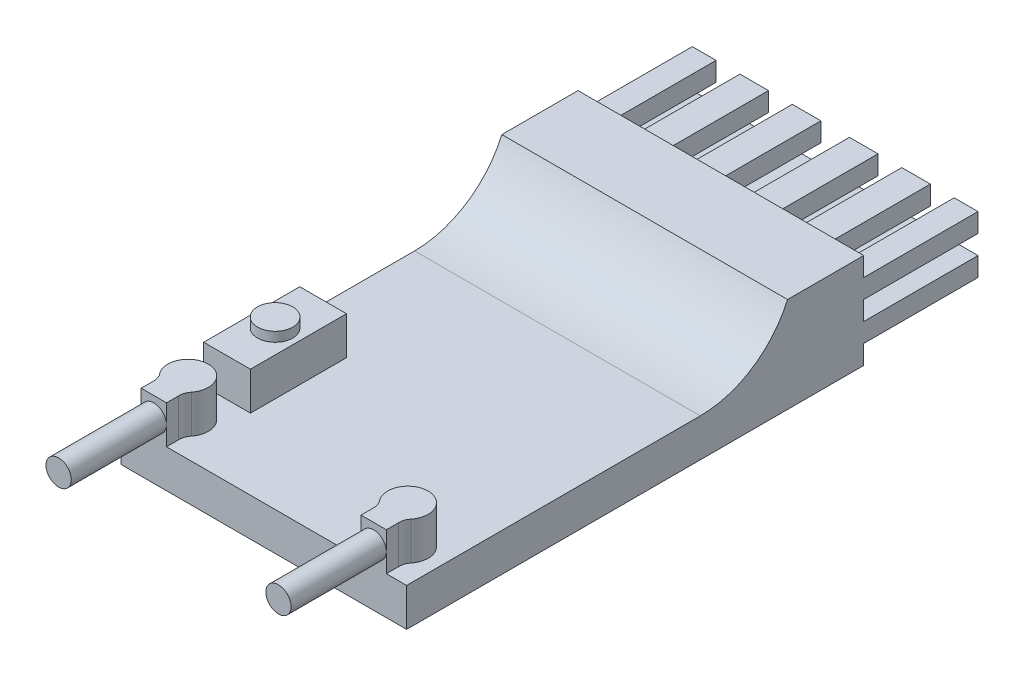
SolidWorks part; units mm, degrees
ref_plane "Front Plane" through (0, 0, 0) normal (0, 0, 1) x (1, 0, 0)
ref_plane "Top Plane" through (0, 0, 0) normal (0, 1, 0) x (1, 0, 0)
ref_plane "Right Plane" through (0, 0, 0) normal (1, 0, 0) x (0, 0, -1)
sketch "Sketch2" plane through (0, 0, 0) normal (0, 1, 0) x (1, 0, 0)
  line L1 (-7.5, 15) -> (7.5, 15)
  line L2 (-7.5, 15) -> (-7.5, -15)
  line L3 (-7.5, -15) -> (7.5, -15)
  line L4 (7.5, 15) -> (7.5, -15)
  line L5 (-7.5, 15) -> (7.5, -15) construction
  line L6 (-7.5, -15) -> (7.5, 15) construction
  point P0 (0, 0)
  dimension "D1" = 30
  dimension "D2" = 15
extrude "Boss-Extrude1" add sketch "Sketch2" along normal blind 2 contours L4 L3 L2 L1
sketch "Sketch3" plane through (7.5, 0, 0) normal (1, 0, 0) x (0, 0, -1)
  line L1 (15, 0) -> (5, 0)
  line L2 (15, 0) -> (15, 5)
  line L3 (15, 5) -> (5, 5)
  line L4 (5, 0) -> (5, 5)
  line L5 (15, 0) -> (5, 5) construction
  line L6 (15, 5) -> (5, 0) construction
  point P4 (10, 2.5)
  dimension "D1" = 5
  dimension "D2" = 10
extrude "Boss-Extrude2" add sketch "Sketch3" against normal up to surface (15 mm away) up to face at (-7.5, 1, 0)
sketch "Sketch4" plane through (7.5, 0, 0) normal (1, 0, 0) x (0, 0, -1)
  line L0 (15, 5) -> (15, 0) construction
  line L1 (15, 0) -> (9, 0)
  line L2 (15, 0) -> (15, 1)
  line L3 (15, 1) -> (9, 1)
  line L4 (9, 0) -> (9, 1)
  line L5 (15, 0) -> (9, 1) construction
  line L6 (15, 1) -> (9, 0) construction
  line L7 (15, 2) -> (9, 2)
  line L8 (15, 2) -> (15, 3)
  line L9 (15, 3) -> (9, 3)
  line L10 (9, 2) -> (9, 3)
  line L11 (15, 2) -> (9, 3) construction
  line L12 (15, 3) -> (9, 2) construction
  line L14 (15, 5) -> (9, 5)
  line L15 (15, 5) -> (15, 4)
  line L16 (15, 4) -> (9, 4)
  line L17 (9, 5) -> (9, 4)
  line L18 (15, 5) -> (9, 4) construction
  line L19 (15, 4) -> (9, 5) construction
  line L20 (15, 5) -> (5, 5) construction
  line L21 (5, 5) -> (5, 2) construction
  point P4 (12, 0.5)
  point P10 (12, 2.5)
  point P17 (12, 4.5)
  dimension "D1" = 1
  dimension "D2" = 1
  dimension "D3" = 1
  dimension "D4" = 4
  dimension "D5" = 1
extrude "Cut-Extrude1" cut sketch "Sketch4" against normal up to surface (15 mm away) up to face at (-7.5, 2.3333, -1.6667)
sketch "Sketch5" plane through (0, 4, 0) normal (0, 1, 0) x (1, 0, 0)
  line L0 (-7.5, 9) -> (7.5, 9) construction
  line L7 (-7.5, 15) -> (7.5, 15) construction
  line L8 (-7.5, 9) -> (7.5, 9) construction
  line L9 (6.25, 9) -> (5, 9)
  line L10 (6.25, 9) -> (6.25, 15)
  line L11 (6.25, 15) -> (5, 15)
  line L12 (5, 9) -> (5, 15)
  line L13 (6.25, 9) -> (5, 15) construction
  line L14 (6.25, 15) -> (5, 9) construction
  line L15 (3.5, 9) -> (2.25, 9)
  line L16 (3.5, 9) -> (3.5, 15)
  line L17 (3.5, 15) -> (2.25, 15)
  line L18 (2.25, 9) -> (2.25, 15)
  line L19 (3.5, 9) -> (2.25, 15) construction
  line L20 (3.5, 15) -> (2.25, 9) construction
  line L22 (0, -2.75) -> (0, 2.75) construction
  line L23 (-3.5, 15) -> (-2.25, 9) construction
  line L24 (-3.5, 9) -> (-2.25, 15) construction
  line L25 (-6.25, 15) -> (-5, 9) construction
  line L26 (-6.25, 9) -> (-5, 15) construction
  line L29 (-2.25, 9) -> (-2.25, 15)
  line L30 (-3.5, 15) -> (-2.25, 15)
  line L31 (-3.5, 9) -> (-3.5, 15)
  line L32 (-3.5, 9) -> (-2.25, 9)
  line L33 (-5, 9) -> (-5, 15)
  line L34 (-6.25, 15) -> (-5, 15)
  line L35 (-6.25, 9) -> (-6.25, 15)
  line L36 (-6.25, 9) -> (-5, 9)
  line L41 (0, 15) -> (-0.75, 9) construction
  line L42 (-0.75, 9) -> (0.75, 9)
  line L43 (0, 9) -> (0, 15)
  line L44 (-0.75, 15) -> (0.75, 15)
  line L45 (0.75, 9) -> (0.75, 15)
  line L46 (0, 9) -> (0.75, 15) construction
  line L47 (0, 15) -> (0.75, 9) construction
  line L48 (0, 9) -> (-0.75, 15) construction
  line L49 (-0.75, 9) -> (-0.75, 15)
  point P13 (5.625, 12)
  point P18 (2.875, 12)
  point P37 (-2.875, 12)
  point P38 (-5.625, 12)
  point P44 (0.375, 12)
  point P47 (-0.375, 12)
  line M11 (-7.5, 9) -> (7.5, 9)
  line M13 (7.5, 15) -> (-7.5, 15)
  dimension "D1" = 1.5
  dimension "D2" = 1.5
  dimension "D3" = 1.25
  dimension "D6" = 1.25
  dimension "D7" = 0.75
extrude "Cut-Extrude2" cut sketch "Sketch5" against normal through all contours L12 L10 M11 M13 | L18 L16 M11 M13 | L42 L45 L43 M13 | L49 L43 M11 M13 | L31 L29 M11 M13 | L35 L33 M11 M13 region at (5.625, 4, -12) region at (2.875, 4, -12) region at (0.375, 4, -12) region at (-0.375, 4, -12) region at (-2.875, 4, -12) region at (-5.625, 4, -12)
fillet "Fillet1" radius 5 1 edges at (0, 2, -5)
sketch "Sketch6" plane through (0, 2, 0) normal (0, 1, 0) x (1, 0, 0)
  line L0 (5.7707, -13.2035) -> (5.7707, -12.1415) construction
  line L1 (5.1061, -14.3698) -> (5.1061, -15)
  line L2 (-7.5, -15) -> (7.5, -15) construction
  line L3 (5.1061, -15) -> (6.4352, -15)
  line L4 (6.4352, -15) -> (6.4352, -14.3698)
  line L5 (0, -2.75) -> (0, 2.75) construction
  line L6 (-5.7707, -13.2035) -> (-5.7707, -12.1415) construction
  line L7 (-6.4352, -15) -> (-6.4352, -14.3698)
  line L8 (-5.1061, -15) -> (-6.4352, -15)
  line L9 (-5.1061, -14.3698) -> (-5.1061, -15)
  arc A0 (4.9405, -13.8658) -> (6.6008, -13.8658) centre (5.7707, -13.2035) cw
  arc A1 (4.9405, -13.8658) -> (5.1061, -14.3698) centre (4.3458, -14.3404) cw
  arc A2 (6.6008, -13.8658) -> (6.4352, -14.3698) centre (7.1956, -14.3404) ccw
  arc A3 (-6.6008, -13.8658) -> (-6.4352, -14.3698) centre (-7.1956, -14.3404) cw
  arc A4 (-4.9405, -13.8658) -> (-5.1061, -14.3698) centre (-4.3458, -14.3404) ccw
  arc A5 (-4.9405, -13.8658) -> (-6.6008, -13.8658) centre (-5.7707, -13.2035) ccw
extrude "Boss-Extrude3" add sketch "Sketch6" along normal blind 2
sketch "Sketch7" plane through (0, 0, 15) normal (0, 0, 1) x (1, 0, 0)
  line L0 (-6.4352, 3) -> (-5.1061, 3) construction
  line L1 (-6.4352, 4) -> (-6.4352, 2) construction
  line L2 (-5.1061, 4) -> (-5.1061, 2) construction
  line L3 (5.1061, 3) -> (6.4352, 3) construction
  line L4 (5.1061, 4) -> (5.1061, 2) construction
  line L5 (6.4352, 4) -> (6.4352, 2) construction
  circle A0 centre (-5.7707, 3) radius 0.6645
  circle A1 centre (5.7707, 3) radius 0.6645
extrude "Boss-Extrude4" add sketch "Sketch7" along normal blind 5
sketch "Sketch8" plane through (0, 2, 0) normal (0, 1, 0) x (1, 0, 0)
  line L1 (-4.4324, -11.2678) -> (-6.887, -11.2678)
  line L2 (-4.4324, -11.2678) -> (-4.4324, -6.224)
  line L3 (-4.4324, -6.224) -> (-6.887, -6.224)
  line L4 (-6.887, -11.2678) -> (-6.887, -6.224)
  line L5 (-4.4324, -11.2678) -> (-6.887, -6.224) construction
  line L6 (-4.4324, -6.224) -> (-6.887, -11.2678) construction
  point P4 (-5.6597, -8.7459)
extrude "Boss-Extrude5" add sketch "Sketch8" along normal up to surface (2 mm away) up to face at (-5.7707, 4, 14.1195)
sketch "Sketch9" plane through (0, 4, 0) normal (0, 1, 0) x (1, 0, 0)
  line L0 (-4.4324, -8.7459) -> (-6.887, -8.7459) construction
  line L1 (-4.4324, -11.2678) -> (-4.4324, -6.224) construction
  line L2 (-6.887, -6.224) -> (-6.887, -11.2678) construction
  circle A0 centre (-5.6597, -8.7459) radius 0.9231
extrude "Boss-Extrude6" add sketch "Sketch9" along normal blind 0.5
